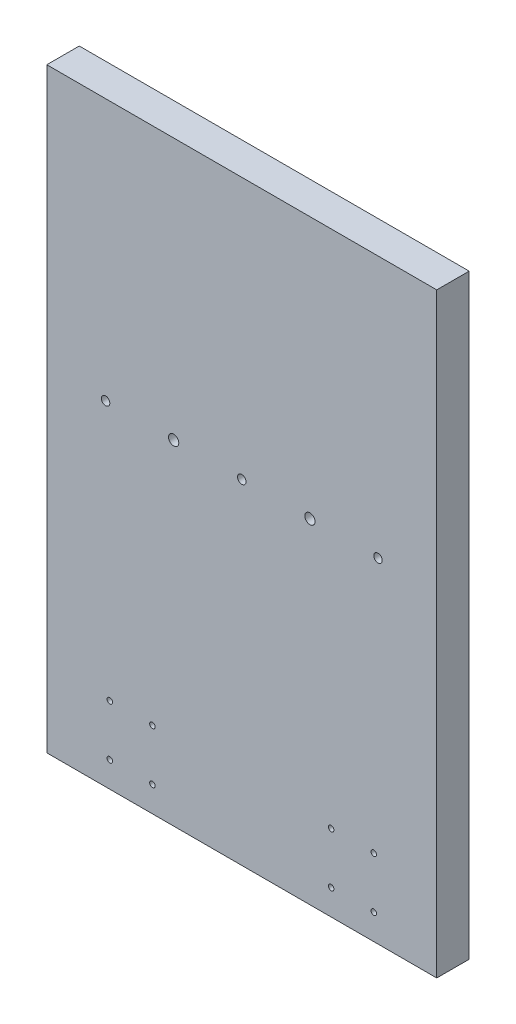
SolidWorks part; units mm, degrees
ref_plane "Front Plane" through (0, 0, 0) normal (0, 0, 1) x (1, 0, 0)
ref_plane "Top Plane" through (0, 0, 0) normal (0, 1, 0) x (1, 0, 0)
ref_plane "Right Plane" through (0, 0, 0) normal (1, 0, 0) x (0, 0, -1)
sketch "Sketch1" plane through (0, 0, 0) normal (0, 0, 1) x (1, 0, 0)
  circle A0 centre (-79.5098, -55.2238) radius 1.621
  circle A1 centre (-54.5098, -55.2238) radius 1.621
  circle A2 centre (-82.0098, 96.1262) radius 2.5
  circle A3 centre (-42.0098, 96.1262) radius 3
  circle A4 centre (-2.0098, 96.1262) radius 2.5
  circle A5 centre (37.9902, 96.1262) radius 3
  circle A6 centre (77.9902, 96.1262) radius 2.5
  circle A7 centre (-79.5098, -85.2238) radius 1.621
  circle A8 centre (-54.5098, -85.2238) radius 1.621
  circle A13 centre (50.4902, -55.2238) radius 1.621
  circle A14 centre (75.4902, -85.2238) radius 1.621
  circle A15 centre (50.4902, -85.2238) radius 1.621
  circle A16 centre (75.4902, -55.2238) radius 1.621
  dimension "D1" = 25
  dimension "D2" = 30
  dimension "D6" = 3.242
  dimension "D7" = 5
  dimension "D8" = 3.242
  dimension "D9" = 6
  dimension "D10" = 3.242
  dimension "D11" = 3.242
  dimension "D12" = 37.9902
  dimension "D13" = 50.4902
  dimension "D14" = 54.5098
  dimension "D15" = 77.9902
  dimension "D17" = 2.0098
  dimension "D18" = 42.0098
  dimension "D20" = 82.0098
  dimension "D21" = 96.1262
  dimension "D23" = 55.2238
  dimension "D3" = 2
sketch "Sketch3" plane through (0, 0, 0) normal (0, 0, 1) x (1, 0, 0)
  line L1 (-99.5098, 89.7762) -> (95.4902, 89.7762)
  line L2 (-99.5098, 89.7762) -> (-99.5098, 102.4762)
  line L3 (-99.5098, 102.4762) -> (95.4902, 102.4762)
  line L4 (95.4902, 89.7762) -> (95.4902, 102.4762)
  dimension "D1" = 95.4902
  dimension "D2" = 99.5098
  dimension "D3" = 89.7762
  dimension "D4" = 102.4762
sketch "Sketch4" plane through (0, 0, 0) normal (0, 0, 1) x (1, 0, 0)
  line L0 (95.4902, 89.7762) -> (95.4902, 102.4762) construction
  line L1 (-116.5098, -100.2238) -> (112.4902, -100.2238)
  line L2 (-116.5098, -100.2238) -> (-116.5098, 249.7762)
  line L3 (-116.5098, 249.7762) -> (112.4902, 249.7762)
  line L4 (112.4902, -100.2238) -> (112.4902, 249.7762)
  line L5 (-99.5098, 89.7762) -> (-99.5098, 102.4762) construction
  circle A0 centre (-79.5098, -85.2238) radius 1.621 construction
  dimension "D2" = 15
  dimension "D1" = 350
  dimension "D3" = 17
  dimension "D4" = 17
extrude "Boss-Extrude1" add sketch "Sketch4" along normal blind 19.05
extrude "Cut-Extrude1" cut sketch "Sketch3" along normal blind 9.525
extrude "Cut-Extrude2" cut sketch "Sketch1" along normal through all
